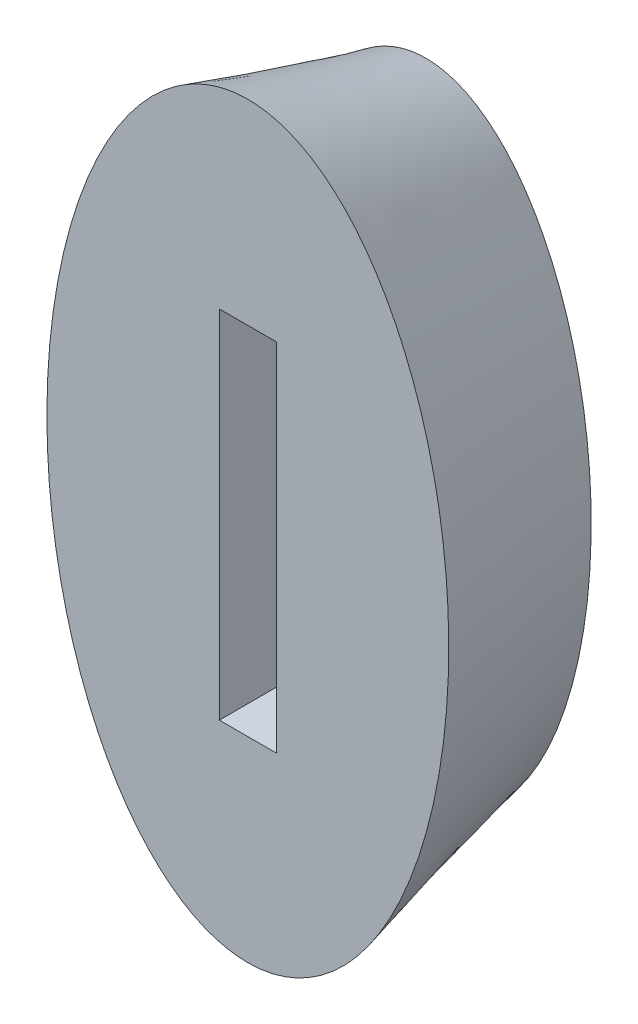
SolidWorks part; units mm, degrees
ref_plane "Front Plane" through (0, 0, 0) normal (0, 0, 1) x (1, 0, 0)
ref_plane "Top Plane" through (0, 0, 0) normal (0, 1, 0) x (1, 0, 0)
ref_plane "Right Plane" through (0, 0, 0) normal (1, 0, 0) x (0, 0, -1)
sketch "Sketch1" plane through (0, 0, 0) normal (0, 0, 1) x (1, 0, 0)
  ellipse E0 centre (0, 0) end of major axis (0, -26.25) minor radius 14.106
  dimension "D1" = 52.5
  dimension "D2" = 28.212
ref_plane "Plane1" through (0, 0, -12.5) normal (0, 0, 1) x (1, 0, 0)
sketch "Sketch2" plane through (0, 0, -12.5) normal (0, 0, 1) x (1, 0, 0)
  ellipse E0 centre (0, 0) end of major axis (0, -22.5) minor radius 11.606
  dimension "D1" = 45
  dimension "D2" = 23.212
sketch "Sketch3" plane through (0, 0, 0) normal (1, 0, 0) x (0, 0, -1)
  line L0 (0, 26.25) -> (12.5, 22.5)
  line L1 (0, -26.25) -> (12.5, -22.5)
loft "Loft1" add profiles "Sketch1", "Sketch2" connector at (13.1796, 9.3558, 0) connector at (9.9674, 11.5264, -12.5)
sketch "Sketch5" plane through (0, 0, 0) normal (0, 0, 1) x (1, 0, 0)
  line L1 (-2, 12.5) -> (2, 12.5)
  line L2 (-2, 12.5) -> (-2, -12.5)
  line L3 (-2, -12.5) -> (2, -12.5)
  line L4 (2, 12.5) -> (2, -12.5)
  line L5 (-2, 12.5) -> (2, -12.5) construction
  line L6 (-2, -12.5) -> (2, 12.5) construction
  point P0 (0, 0)
  dimension "D1" = 4
  dimension "D2" = 25
extrude "Cut-Extrude1" cut sketch "Sketch5" against normal blind 30
sketch "Sketch6" plane through (0, 0, -12.5) normal (0, 0, -1) x (-1, 0, 0)
  line L1 (-4.0091, 15.0342) -> (4.0091, 15.0342)
  line L2 (-4.0091, 15.0342) -> (-4.0091, -15.0342)
  line L3 (-4.0091, -15.0342) -> (4.0091, -15.0342)
  line L4 (4.0091, 15.0342) -> (4.0091, -15.0342)
  line L5 (-4.0091, 15.0342) -> (4.0091, -15.0342) construction
  line L6 (-4.0091, -15.0342) -> (4.0091, 15.0342) construction
  ellipse E0 centre (0, 0) end of major axis (0, -19.3106) minor radius 9.8892
  point P0 (0, 0)
extrude "Cut-Extrude2" cut sketch "Sketch6" against normal blind 7.5
